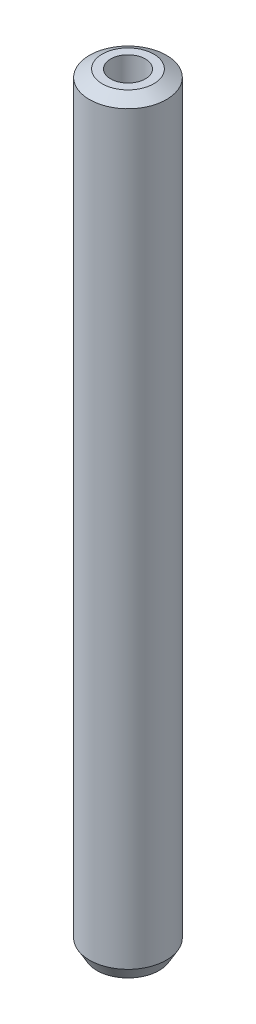
SolidWorks part; units mm, degrees
ref_plane "Front Plane" through (0, 0, 0) normal (0, 0, 1) x (1, 0, 0)
ref_plane "Top Plane" through (0, 0, 0) normal (0, 1, 0) x (1, 0, 0)
ref_plane "Right Plane" through (0, 0, 0) normal (1, 0, 0) x (0, 0, -1)
sketch "Sketch1" plane through (0, 0, 0) normal (0, 1, 0) x (1, 0, 0)
  circle A0 centre (0, 0) radius 10
  dimension "SHAFT_OD" = 20
extrude "Boss-Extrude1" add sketch "Sketch1" along normal blind 199.0332
sketch "Sketch2" plane through (0, 0, 0) normal (0, 1, 0) x (1, 0, 0)
  circle A0 centre (0, 0) radius 4.5075
  dimension "BORE_D" = 9.0151
extrude "Cut-Extrude1" cut sketch "Sketch2" along normal through all
chamfer "Chamfer1" distance 1.9064 angle 60 2 edges at (0, 199.0332, 10) (0, 0, 10) first distance on face at (0, 199.0332, 10) first distance on face at (0, 0, 4.5075)
